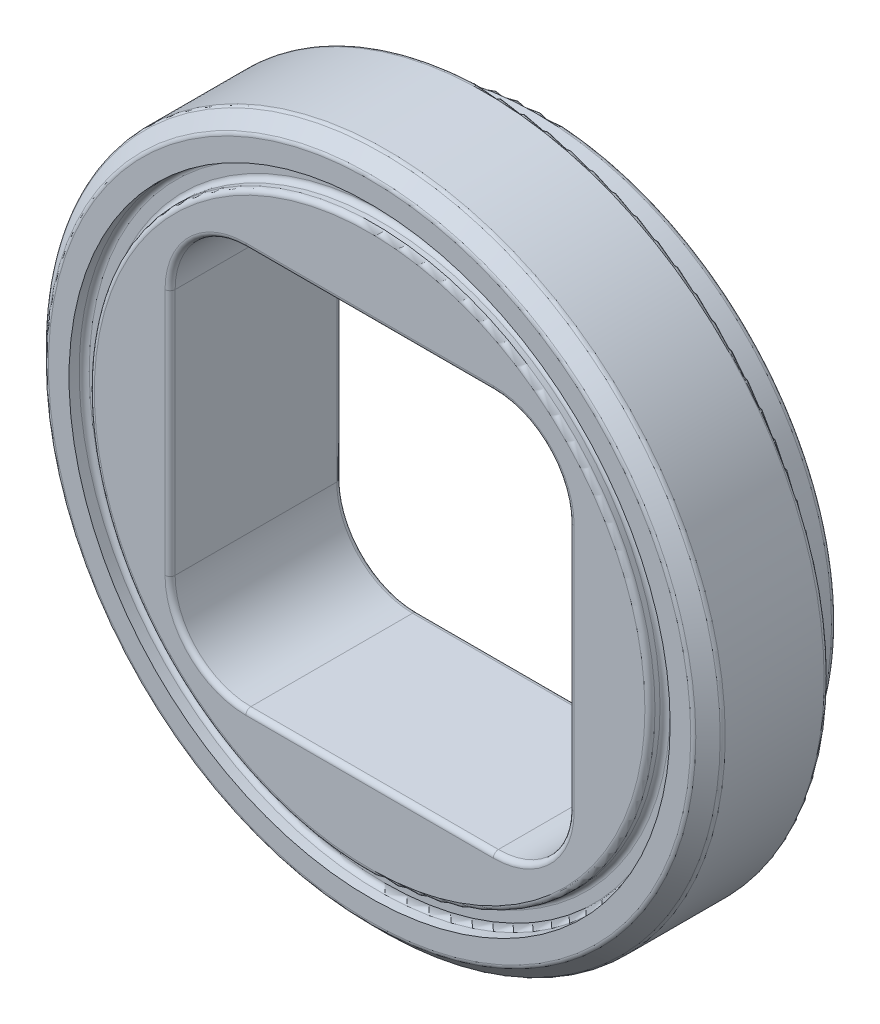
SolidWorks part; units mm, degrees
material "moto_black"
ref_plane "Front Plane" through (0, 0, 0) normal (0, 0, 1) x (1, 0, 0)
ref_plane "Top Plane" through (0, 0, 0) normal (0, 1, 0) x (1, 0, 0)
ref_plane "Right Plane" through (0, 0, 0) normal (1, 0, 0) x (0, 0, -1)
sketch "Sketch1" plane through (0, 0, 0) normal (0, 0, 1) x (1, 0, 0)
  line L1 (-24.5, 39.5) -> (24.5, 39.5)
  line L2 (-39.5, 24.5) -> (-39.5, -24.5)
  line L3 (-24.5, -39.5) -> (24.5, -39.5)
  line L4 (39.5, 24.5) -> (39.5, -24.5)
  line L5 (-39.5, 39.5) -> (39.5, -39.5) construction
  line L6 (-39.5, -39.5) -> (39.5, 39.5) construction
  circle A0 centre (0, 0) radius 67
  arc A1 (-39.5, -24.5) -> (-24.5, -39.5) centre (-24.5, -24.5) ccw
  arc A2 (24.5, 39.5) -> (39.5, 24.5) centre (24.5, 24.5) cw
  arc A3 (24.5, -39.5) -> (39.5, -24.5) centre (24.5, -24.5) ccw
  arc A4 (-24.5, 39.5) -> (-39.5, 24.5) centre (-24.5, 24.5) ccw
  circle A5 centre (0, 0) radius 59.5057
  circle A6 centre (0, 0) radius 55.5057
  dimension "D1" = 134
  dimension "D4" = 15
  dimension "D2" = 79
  dimension "D3" = 79
  dimension "D5" = 4
extrude "Boss-Extrude1" add sketch "Sketch1" against normal blind 24 contours A0 A5 | A6 A4 L1 A2 L4 A3 L3 A1 L2 | A5 A6 region at (-65.105, 0, 0) region at (-57.8226, 0, 0) region at (-53.9358, 0, 0)
extrude "Cut-Extrude1" cut sketch "Sketch1<4>" against normal blind 3 contours A5 A6 region at (-57.8226, 0, 0)
sketch "Sketch1<4>" plane through (0, 0, 0) normal (0, 0, 1) x (1, 0, 0) same geometry as "Sketch1"
sketch "Sketch2" plane through (0, 0, -24) normal (0, 0, -1) x (-1, 0, 0)
  line L28 (39.5, -24.5) -> (39.5, 24.5)
  line L29 (-24.5, -39.5) -> (24.5, -39.5)
  line L30 (-39.5, 24.5) -> (-39.5, -24.5)
  line L31 (24.5, 39.5) -> (-24.5, 39.5)
  line L32 (39.5, -24.5) -> (39.5, 24.5)
  line L33 (-24.5, -39.5) -> (24.5, -39.5)
  line L34 (-39.5, 24.5) -> (-39.5, -24.5)
  line L35 (24.5, 39.5) -> (-24.5, 39.5)
  circle A0 centre (0, 0) radius 58.4657
  circle A1 centre (0, 0) radius 54.4657
  arc A28 (39.5, 24.5) -> (24.5, 39.5) centre (24.5, 24.5) ccw
  arc A29 (24.5, -39.5) -> (39.5, -24.5) centre (24.5, -24.5) ccw
  arc A30 (-39.5, -24.5) -> (-24.5, -39.5) centre (-24.5, -24.5) ccw
  arc A31 (-24.5, 39.5) -> (-39.5, 24.5) centre (-24.5, 24.5) ccw
  arc A32 (39.5, 24.5) -> (24.5, 39.5) centre (24.5, 24.5) ccw
  arc A33 (24.5, -39.5) -> (39.5, -24.5) centre (24.5, -24.5) ccw
  arc A34 (-39.5, -24.5) -> (-24.5, -39.5) centre (-24.5, -24.5) ccw
  arc A35 (-24.5, 39.5) -> (-39.5, 24.5) centre (-24.5, 24.5) ccw
  arc M4 (24.5, 39.5) -> (39.5, 24.5) centre (24.5, 24.5) cw
  line M5 (39.5, 24.5) -> (39.5, -24.5)
  arc M6 (39.5, -24.5) -> (24.5, -39.5) centre (24.5, -24.5) cw
  line M7 (24.5, -39.5) -> (-24.5, -39.5)
  arc M8 (-24.5, -39.5) -> (-39.5, -24.5) centre (-24.5, -24.5) cw
  line M9 (-39.5, -24.5) -> (-39.5, 24.5)
  arc M10 (-39.5, 24.5) -> (-24.5, 39.5) centre (-24.5, 24.5) cw
  line M11 (-24.5, 39.5) -> (24.5, 39.5)
  dimension "D1" = 4
  dimension "D2" = 0
extrude "Boss-Extrude2" add sketch "Sketch2" along normal blind 10 contours A1 M11 M4 M5 M6 M7 M8 M9 M10 | A0 A1 region at (56.812, 0, -24) region at (52.9251, 0, -24)
chamfer "Chamfer1" distance 5 angle 45 1 edges at (-58.4657, 0, -24)
chamfer "Chamfer2" distance 3 angle 45 1 edges at (67, 0, 0)
fillet "Fillet1" radius 1 25 edges at (35.1066, 35.1066, -34) (39.5, 0, -34) (35.1066, -35.1066, -34) (0, -39.5, -34) (-35.1066, -35.1066, -34) (-39.5, 0, -34) (-35.1066, 35.1066, -34) (0, 39.5, 0) (-35.1066, 35.1066, 0) (-39.5, 0, 0) (-35.1066, -35.1066, 0) (0, -39.5, 0) (35.1066, -35.1066, 0) (39.5, 0, 0) (64, 0, 0) (59.5057, 0, -3) (55.5057, 0, -3) (0, 39.5, -34) (-58.4657, 0, -34) (58.4657, 0, -29) (63.4657, 0, -24) (67, 0, -24) (35.1066, 35.1066, 0) (55.5057, 0, 0) (67, 0, -3)
